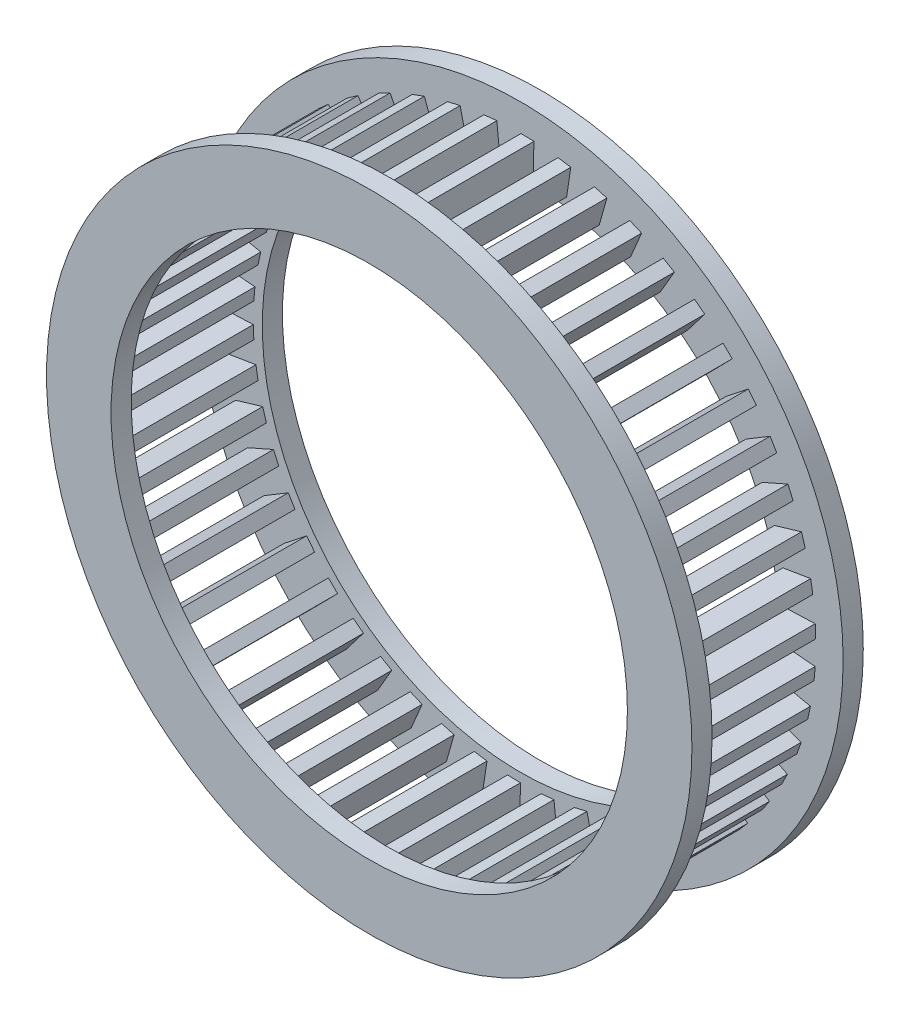
SolidWorks part; units mm, degrees
ref_plane "Спереди" through (0, 0, 0) normal (0, 0, 1) x (1, 0, 0)
ref_plane "Сверху" through (0, 0, 0) normal (0, 1, 0) x (1, 0, 0)
ref_plane "Справа" through (0, 0, 0) normal (1, 0, 0) x (0, 0, -1)
sketch "Эскиз1" plane through (0, 0, 0) normal (0, 0, 1) x (1, 0, 0)
  line L0 (61.1496, 0.9053) -> (67.6062, 1.1569)
  line L1 (67.6062, 1.1569) -> (67.4912, 4.1085)
  line L2 (67.4912, 4.1085) -> (61.0346, 3.8569)
  line L3 (61.0346, 3.8569) -> (61.1496, 0.9053)
  line L4 (60.554, 8.5622) -> (66.9281, 9.6211)
  line L5 (66.9281, 9.6211) -> (66.4441, 12.535)
  line L6 (66.4441, 12.535) -> (60.0699, 11.4761)
  line L7 (60.0699, 11.4761) -> (60.554, 8.5622)
  line L8 (59.0033, 16.0841) -> (65.1945, 17.9336)
  line L9 (65.1945, 17.9336) -> (64.3491, 20.7638)
  line L10 (64.3491, 20.7638) -> (58.1579, 18.9144)
  line L11 (58.1579, 18.9144) -> (59.0033, 16.0841)
  line L12 (56.5222, 23.3524) -> (62.4328, 25.9632)
  line L13 (62.4328, 25.9632) -> (61.2393, 28.6652)
  line L14 (61.2393, 28.6652) -> (55.3287, 26.0544)
  line L15 (55.3287, 26.0544) -> (56.5222, 23.3524)
  line L16 (53.1497, 30.2524) -> (58.6864, 33.5834)
  line L17 (58.6864, 33.5834) -> (57.1637, 36.1145)
  line L18 (57.1637, 36.1145) -> (51.6269, 32.7834)
  line L19 (51.6269, 32.7834) -> (53.1497, 30.2524)
  line L20 (48.9389, 36.6752) -> (54.0146, 40.6739)
  line L21 (54.0146, 40.6739) -> (52.1866, 42.9942)
  line L22 (52.1866, 42.9942) -> (47.111, 38.9955)
  line L23 (47.111, 38.9955) -> (48.9389, 36.6752)
  line L24 (43.9564, 42.5197) -> (48.4908, 47.123)
  line L25 (48.4908, 47.123) -> (46.3865, 49.1959)
  line L26 (46.3865, 49.1959) -> (41.8521, 44.5926)
  line L27 (41.8521, 44.5926) -> (43.9564, 42.5197)
  line L28 (38.2807, 47.6936) -> (42.2024, 52.829)
  line L29 (42.2024, 52.829) -> (39.8548, 54.6217)
  line L30 (39.8548, 54.6217) -> (35.9331, 49.4864)
  line L31 (35.9331, 49.4864) -> (38.2807, 47.6936)
  line L32 (32.0012, 52.1154) -> (35.2484, 57.7018)
  line L33 (35.2484, 57.7018) -> (32.6946, 59.1862)
  line L34 (32.6946, 59.1862) -> (29.4475, 53.5998)
  line L35 (29.4475, 53.5998) -> (32.0012, 52.1154)
  line L36 (25.2171, 55.7153) -> (27.7385, 61.6645)
  line L37 (27.7385, 61.6645) -> (25.0188, 62.8172)
  line L38 (25.0188, 62.8172) -> (22.4974, 56.8679)
  line L39 (22.4974, 56.8679) -> (25.2171, 55.7153)
  line L40 (18.0353, 58.4365) -> (19.7912, 64.6549)
  line L41 (19.7912, 64.6549) -> (16.9485, 65.4575)
  line L42 (16.9485, 65.4575) -> (15.1926, 59.2392)
  line L43 (15.1926, 59.2392) -> (18.0353, 58.4365)
  line L44 (10.569, 60.2361) -> (11.5317, 66.6255)
  line L45 (11.5317, 66.6255) -> (8.6108, 67.0656)
  line L46 (8.6108, 67.0656) -> (7.6482, 60.6762)
  line L47 (7.6482, 60.6762) -> (10.569, 60.2361)
  line L48 (2.9361, 61.0858) -> (3.0904, 67.5455)
  line L49 (3.0904, 67.5455) -> (0.1374, 67.616)
  line L50 (0.1374, 67.616) -> (-0.0169, 61.1563)
  line L51 (-0.0169, 61.1563) -> (2.9361, 61.0858)
  line L52 (-4.7431, 60.9721) -> (-5.3997, 67.4002)
  line L53 (-5.3997, 67.4002) -> (-8.3382, 67.1)
  line L54 (-8.3382, 67.1) -> (-7.6817, 60.6719)
  line L55 (-7.6817, 60.6719) -> (-4.7431, 60.9721)
  line L56 (-12.3475, 59.8968) -> (-13.8046, 66.192)
  line L57 (-13.8046, 66.192) -> (-16.6824, 65.5259)
  line L58 (-16.6824, 65.5259) -> (-15.2253, 59.2308)
  line L59 (-15.2253, 59.2308) -> (-12.3475, 59.8968)
  line L60 (-19.7572, 57.877) -> (-21.9918, 63.9398)
  line L61 (-21.9918, 63.9398) -> (-24.7634, 62.9183)
  line L62 (-24.7634, 62.9183) -> (-22.5288, 56.8555)
  line L63 (-22.5288, 56.8555) -> (-19.7572, 57.877)
  line L64 (-26.8554, 54.9444) -> (-29.8322, 60.6793)
  line L65 (-29.8322, 60.6793) -> (-32.4539, 59.3185)
  line L66 (-32.4539, 59.3185) -> (-29.4771, 53.5835)
  line L67 (-29.4771, 53.5835) -> (-26.8554, 54.9444)
  line L68 (-33.53, 51.1452) -> (-37.2021, 56.4619)
  line L69 (-37.2021, 56.4619) -> (-39.6325, 54.7832)
  line L70 (-39.6325, 54.7832) -> (-35.9604, 49.4666)
  line L71 (-35.9604, 49.4666) -> (-33.53, 51.1452)
  line L72 (-39.6758, 46.5395) -> (-43.9853, 51.354)
  line L73 (-43.9853, 51.354) -> (-46.1862, 49.384)
  line L74 (-46.1862, 49.384) -> (-41.8767, 44.5695)
  line L75 (-41.8767, 44.5695) -> (-39.6758, 46.5395)
  line L76 (-45.1959, 41.1999) -> (-50.0748, 45.4363)
  line L77 (-50.0748, 45.4363) -> (-52.0115, 43.2059)
  line L78 (-52.0115, 43.2059) -> (-47.1325, 38.9695)
  line L79 (-47.1325, 38.9695) -> (-45.1959, 41.1999)
  line L80 (-50.0032, 35.2104) -> (-55.3746, 38.802)
  line L81 (-55.3746, 38.802) -> (-57.0165, 36.3464)
  line L82 (-57.0165, 36.3464) -> (-51.645, 32.7549)
  line L83 (-51.645, 32.7549) -> (-50.0032, 35.2104)
  line L84 (-54.0219, 28.6657) -> (-59.8012, 31.5557)
  line L85 (-59.8012, 31.5557) -> (-61.1223, 28.9138)
  line L86 (-61.1223, 28.9138) -> (-55.3431, 26.0238)
  line L87 (-55.3431, 26.0238) -> (-54.0219, 28.6657)
  line L88 (-57.1887, 21.669) -> (-63.2846, 23.8118)
  line L89 (-63.2846, 23.8118) -> (-64.2642, 21.0251)
  line L90 (-64.2642, 21.0251) -> (-58.1683, 18.8823)
  line L91 (-58.1683, 18.8823) -> (-57.1887, 21.669)
  line L92 (-59.4536, 14.3304) -> (-65.77, 15.6924)
  line L93 (-65.77, 15.6924) -> (-66.3926, 12.8049)
  line L94 (-66.3926, 12.8049) -> (-60.0762, 11.443)
  line L95 (-60.0762, 11.443) -> (-59.4536, 14.3304)
  line L96 (-60.7809, 6.7659) -> (-67.2181, 7.3255)
  line L97 (-67.2181, 7.3255) -> (-67.4739, 4.3827)
  line L98 (-67.4739, 4.3827) -> (-61.0367, 3.8232)
  line L99 (-61.0367, 3.8232) -> (-60.7809, 6.7659)
  line L100 (-61.1496, -0.9053) -> (-67.6062, -1.1569)
  line L101 (-67.6062, -1.1569) -> (-67.4912, -4.1085)
  line L102 (-67.4912, -4.1085) -> (-61.0346, -3.8569)
  line L103 (-61.0346, -3.8569) -> (-61.1496, -0.9053)
  line L104 (-60.554, -8.5622) -> (-66.9281, -9.6211)
  line L105 (-66.9281, -9.6211) -> (-66.4441, -12.535)
  line L106 (-66.4441, -12.535) -> (-60.0699, -11.4761)
  line L107 (-60.0699, -11.4761) -> (-60.554, -8.5622)
  line L108 (-59.0033, -16.0841) -> (-65.1945, -17.9336)
  line L109 (-65.1945, -17.9336) -> (-64.3491, -20.7638)
  line L110 (-64.3491, -20.7638) -> (-58.1579, -18.9144)
  line L111 (-58.1579, -18.9144) -> (-59.0033, -16.0841)
  line L112 (-56.5222, -23.3524) -> (-62.4328, -25.9632)
  line L113 (-62.4328, -25.9632) -> (-61.2393, -28.6652)
  line L114 (-61.2393, -28.6652) -> (-55.3287, -26.0544)
  line L115 (-55.3287, -26.0544) -> (-56.5222, -23.3524)
  line L116 (-53.1497, -30.2524) -> (-58.6864, -33.5834)
  line L117 (-58.6864, -33.5834) -> (-57.1637, -36.1145)
  line L118 (-57.1637, -36.1145) -> (-51.6269, -32.7834)
  line L119 (-51.6269, -32.7834) -> (-53.1497, -30.2524)
  line L120 (-48.9389, -36.6752) -> (-54.0146, -40.6739)
  line L121 (-54.0146, -40.6739) -> (-52.1866, -42.9942)
  line L122 (-52.1866, -42.9942) -> (-47.111, -38.9955)
  line L123 (-47.111, -38.9955) -> (-48.9389, -36.6752)
  line L124 (-43.9564, -42.5197) -> (-48.4908, -47.123)
  line L125 (-48.4908, -47.123) -> (-46.3865, -49.1959)
  line L126 (-46.3865, -49.1959) -> (-41.8521, -44.5926)
  line L127 (-41.8521, -44.5926) -> (-43.9564, -42.5197)
  line L128 (-38.2807, -47.6936) -> (-42.2024, -52.829)
  line L129 (-42.2024, -52.829) -> (-39.8548, -54.6217)
  line L130 (-39.8548, -54.6217) -> (-35.9331, -49.4864)
  line L131 (-35.9331, -49.4864) -> (-38.2807, -47.6936)
  line L132 (-32.0012, -52.1154) -> (-35.2484, -57.7018)
  line L133 (-35.2484, -57.7018) -> (-32.6946, -59.1862)
  line L134 (-32.6946, -59.1862) -> (-29.4475, -53.5998)
  line L135 (-29.4475, -53.5998) -> (-32.0012, -52.1154)
  line L136 (-25.2171, -55.7153) -> (-27.7385, -61.6645)
  line L137 (-27.7385, -61.6645) -> (-25.0188, -62.8172)
  line L138 (-25.0188, -62.8172) -> (-22.4974, -56.8679)
  line L139 (-22.4974, -56.8679) -> (-25.2171, -55.7153)
  line L140 (-18.0353, -58.4365) -> (-19.7912, -64.6549)
  line L141 (-19.7912, -64.6549) -> (-16.9485, -65.4575)
  line L142 (-16.9485, -65.4575) -> (-15.1926, -59.2392)
  line L143 (-15.1926, -59.2392) -> (-18.0353, -58.4365)
  line L144 (-10.569, -60.2361) -> (-11.5317, -66.6255)
  line L145 (-11.5317, -66.6255) -> (-8.6108, -67.0656)
  line L146 (-8.6108, -67.0656) -> (-7.6482, -60.6762)
  line L147 (-7.6482, -60.6762) -> (-10.569, -60.2361)
  line L148 (-2.9361, -61.0858) -> (-3.0904, -67.5455)
  line L149 (-3.0904, -67.5455) -> (-0.1374, -67.616)
  line L150 (-0.1374, -67.616) -> (0.0169, -61.1563)
  line L151 (0.0169, -61.1563) -> (-2.9361, -61.0858)
  line L152 (4.7431, -60.9721) -> (5.3997, -67.4002)
  line L153 (5.3997, -67.4002) -> (8.3382, -67.1)
  line L154 (8.3382, -67.1) -> (7.6817, -60.6719)
  line L155 (7.6817, -60.6719) -> (4.7431, -60.9721)
  line L156 (12.3475, -59.8968) -> (13.8046, -66.192)
  line L157 (13.8046, -66.192) -> (16.6824, -65.5259)
  line L158 (16.6824, -65.5259) -> (15.2253, -59.2308)
  line L159 (15.2253, -59.2308) -> (12.3475, -59.8968)
  line L160 (19.7572, -57.877) -> (21.9918, -63.9398)
  line L161 (21.9918, -63.9398) -> (24.7634, -62.9183)
  line L162 (24.7634, -62.9183) -> (22.5288, -56.8555)
  line L163 (22.5288, -56.8555) -> (19.7572, -57.877)
  line L164 (26.8554, -54.9444) -> (29.8322, -60.6793)
  line L165 (29.8322, -60.6793) -> (32.4539, -59.3185)
  line L166 (32.4539, -59.3185) -> (29.4771, -53.5835)
  line L167 (29.4771, -53.5835) -> (26.8554, -54.9444)
  line L168 (33.53, -51.1452) -> (37.2021, -56.4619)
  line L169 (37.2021, -56.4619) -> (39.6325, -54.7832)
  line L170 (39.6325, -54.7832) -> (35.9604, -49.4666)
  line L171 (35.9604, -49.4666) -> (33.53, -51.1452)
  line L172 (39.6758, -46.5395) -> (43.9853, -51.354)
  line L173 (43.9853, -51.354) -> (46.1862, -49.384)
  line L174 (46.1862, -49.384) -> (41.8767, -44.5695)
  line L175 (41.8767, -44.5695) -> (39.6758, -46.5395)
  line L176 (45.1959, -41.1999) -> (50.0748, -45.4363)
  line L177 (50.0748, -45.4363) -> (52.0115, -43.2059)
  line L178 (52.0115, -43.2059) -> (47.1325, -38.9695)
  line L179 (47.1325, -38.9695) -> (45.1959, -41.1999)
  line L180 (50.0032, -35.2104) -> (55.3746, -38.802)
  line L181 (55.3746, -38.802) -> (57.0165, -36.3464)
  line L182 (57.0165, -36.3464) -> (51.645, -32.7549)
  line L183 (51.645, -32.7549) -> (50.0032, -35.2104)
  line L184 (54.0219, -28.6657) -> (59.8012, -31.5557)
  line L185 (59.8012, -31.5557) -> (61.1223, -28.9138)
  line L186 (61.1223, -28.9138) -> (55.3431, -26.0238)
  line L187 (55.3431, -26.0238) -> (54.0219, -28.6657)
  line L188 (57.1887, -21.669) -> (63.2846, -23.8118)
  line L189 (63.2846, -23.8118) -> (64.2642, -21.0251)
  line L190 (64.2642, -21.0251) -> (58.1683, -18.8823)
  line L191 (58.1683, -18.8823) -> (57.1887, -21.669)
  line L192 (59.4536, -14.3304) -> (65.77, -15.6924)
  line L193 (65.77, -15.6924) -> (66.3926, -12.8049)
  line L194 (66.3926, -12.8049) -> (60.0762, -11.443)
  line L195 (60.0762, -11.443) -> (59.4536, -14.3304)
  line L196 (60.7809, -6.7659) -> (67.2181, -7.3255)
  line L197 (67.2181, -7.3255) -> (67.4739, -4.3827)
  line L198 (67.4739, -4.3827) -> (61.0367, -3.8232)
  line L199 (61.0367, -3.8232) -> (60.7809, -6.7659)
extrude "Cage_50_bars" add sketch "Эскиз1" along normal blind 30.2 from offset 15.1 separate body offset against normal yes
sketch "Эскиз2" plane through (0, 0, 0) normal (0, 0, 1) x (1, 0, 0)
  circle A0 centre (0, 0) radius 73.8769
  circle A1 centre (0, 0) radius 59.1077
extrude "Cage_ring_right" add sketch "Эскиз2" along normal blind 4.6154 from offset 15
sketch "Эскиз3" plane through (0, 0, 0) normal (0, 0, 1) x (1, 0, 0)
  circle A0 centre (0, 0) radius 73.8769
  circle A1 centre (0, 0) radius 59.1077
extrude "Cage_ring_left" add sketch "Эскиз3" along normal blind 4.6154 from offset 19.6154 offset against normal yes
